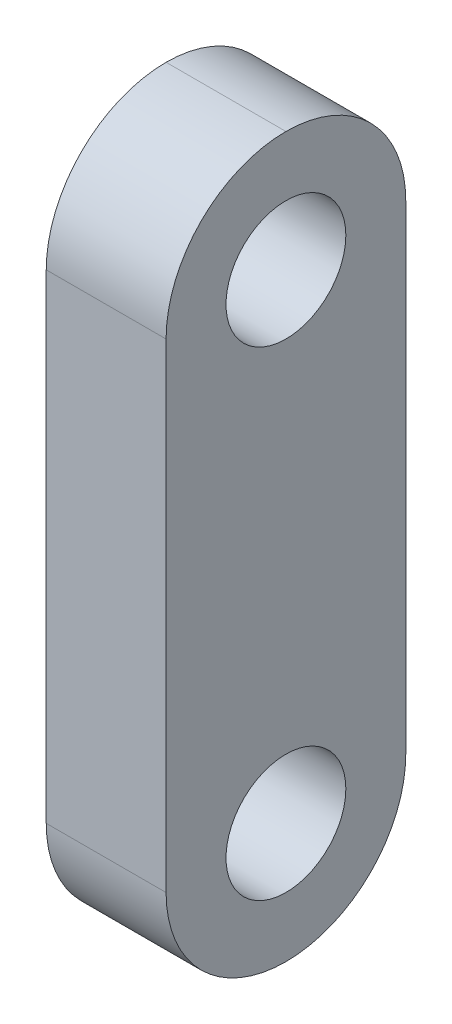
SolidWorks part; units mm, degrees
material "6061-T6 (SS)"
ref_plane "Front Plane" through (0, 0, 0) normal (0, 0, 1) x (1, 0, 0)
ref_plane "Top Plane" through (0, 0, 0) normal (0, 1, 0) x (1, 0, 0)
ref_plane "Right Plane" through (0, 0, 0) normal (1, 0, 0) x (0, 0, -1)
sketch "Sketch1" plane through (0, 0, 0) normal (1, 0, 0) x (0, 0, -1)
  line L0 (0, 0) -> (0, -6.35) construction
  line L1 (-3.175, -15.875) -> (3.175, -15.875)
  line L2 (-3.175, -15.875) -> (-3.175, 3.175)
  line L3 (-3.175, 3.175) -> (3.175, 3.175)
  line L4 (3.175, -15.875) -> (3.175, 3.175)
  line L5 (-3.175, -15.875) -> (3.175, 3.175) construction
  line L6 (-3.175, 3.175) -> (3.175, -15.875) construction
  line L7 (0, -6.35) -> (0, -12.7) construction
  circle A0 centre (0, 0) radius 1.5875
  circle A1 centre (0, -12.7) radius 1.5875
  point P5 (0, -6.35)
  dimension "D1" = 3.175
  dimension "D2" = 6.35
  dimension "D3" = 19.05
  dimension "D4" = 6.35
extrude "Boss-Extrude1" add sketch "Sketch1" along normal blind 1.5875 and the other way blind 1.5875
fillet "Fillet1" radius 3.175 4 edges at (0, -15.875, -3.175) (0, -15.875, 3.175) (0, 3.175, -3.175) (0, 3.175, 3.175)
